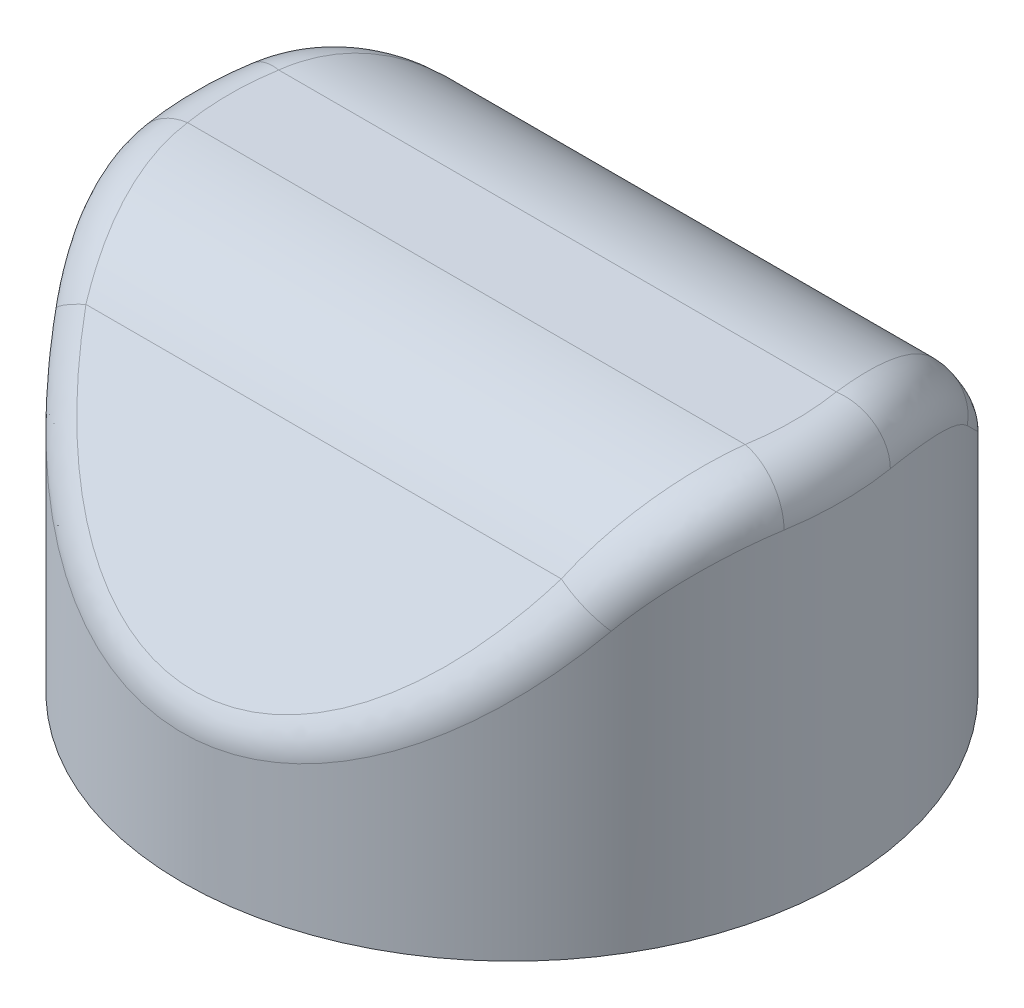
SolidWorks part; units mm, degrees
ref_plane "Спереди" through (0, 0, 0) normal (0, 0, 1) x (1, 0, 0)
ref_plane "Сверху" through (0, 0, 0) normal (0, 1, 0) x (1, 0, 0)
ref_plane "Справа" through (0, 0, 0) normal (1, 0, 0) x (0, 0, -1)
sketch "Sketch1" plane through (0, 0, 0) normal (0, 1, 0) x (1, 0, 0)
  circle A0 centre (0, 0) radius 7
  dimension "D1" = 14
extrude "Boss-Extrude1" add sketch "Sketch1" along normal blind 8
sketch "Sketch2" plane through (0, 0, 0) normal (1, 0, 0) x (0, 0, -1)
  line L0 (-7, 3.1216) -> (7, 3.1216) construction
  line L1 (-7, 8) -> (-7, 0) construction
  line L2 (7, 3.1216) -> (4, 6.6087)
  line L3 (0.9677, 8) -> (-0.9677, 8)
  line L4 (-4, 6.6087) -> (-7, 3.1216)
  line L5 (7, 8) -> (-7, 8) construction
  line L6 (7, 3.1216) -> (7, 0)
  line L7 (7, 0) -> (-7, 0)
  line L8 (-7, 0) -> (-7, 3.1216)
  line L9 (-7, 0) -> (7, 0) construction
  arc A0 (0.9677, 8) -> (4, 6.6087) centre (0.9677, 4) cw
  arc A1 (-4, 6.6087) -> (-0.9677, 8) centre (-0.9677, 4) cw
  dimension "D1" = 4
  dimension "D2" = 14
  dimension "D3" = 8
  dimension "D4" = 4.6
extrude "Cut-Extrude1" cut sketch "Sketch2" against normal through all both and the other way through all flip side to cut
sketch "Sketch3" plane through (0, 0, 0) normal (0, -1, 0) x (1, 0, 0)
  line L0 (0, -7) -> (0, 7) construction
  line L1 (0, 1.4142) -> (-1.4142, 0)
  line L2 (0, 1.4142) -> (1.4142, 0)
  line L3 (-1.4142, 0) -> (0, -1.4142)
  line L4 (1.4142, 0) -> (0, -1.4142)
  line L5 (-0.7071, -0.7071) -> (0.7071, 0.7071) construction
  line L6 (-0.7071, 0.7071) -> (0.7071, -0.7071) construction
  circle A0 centre (0, 0) radius 7 construction
  point P5 (0, 0)
  point P6 (0, 0)
  point P7 (0, 8)
  dimension "D1" = 2
extrude "Cut-Extrude2" cut sketch "Sketch3" against normal blind 2.2
chamfer "Chamfer1" distance 0.2 angle 60 4 edges at (-0.7071, 0, 0.7071) (0.7071, 0, 0.7071) (0.7071, 0, -0.7071) (-0.7071, 0, -0.7071) first distance on face at (0, 0, 0)
fillet "Fillet1" radius 1 8 edges at (0, 3.1216, -7) (6.6394, 7.7996, -2.2178) (7, 8, 0) (6.368, 7.4987, 2.9066) (0, 3.1216, 7) (-6.6394, 7.7996, 2.2178) (-7, 8, 0) (-6.368, 7.4987, -2.9066)
